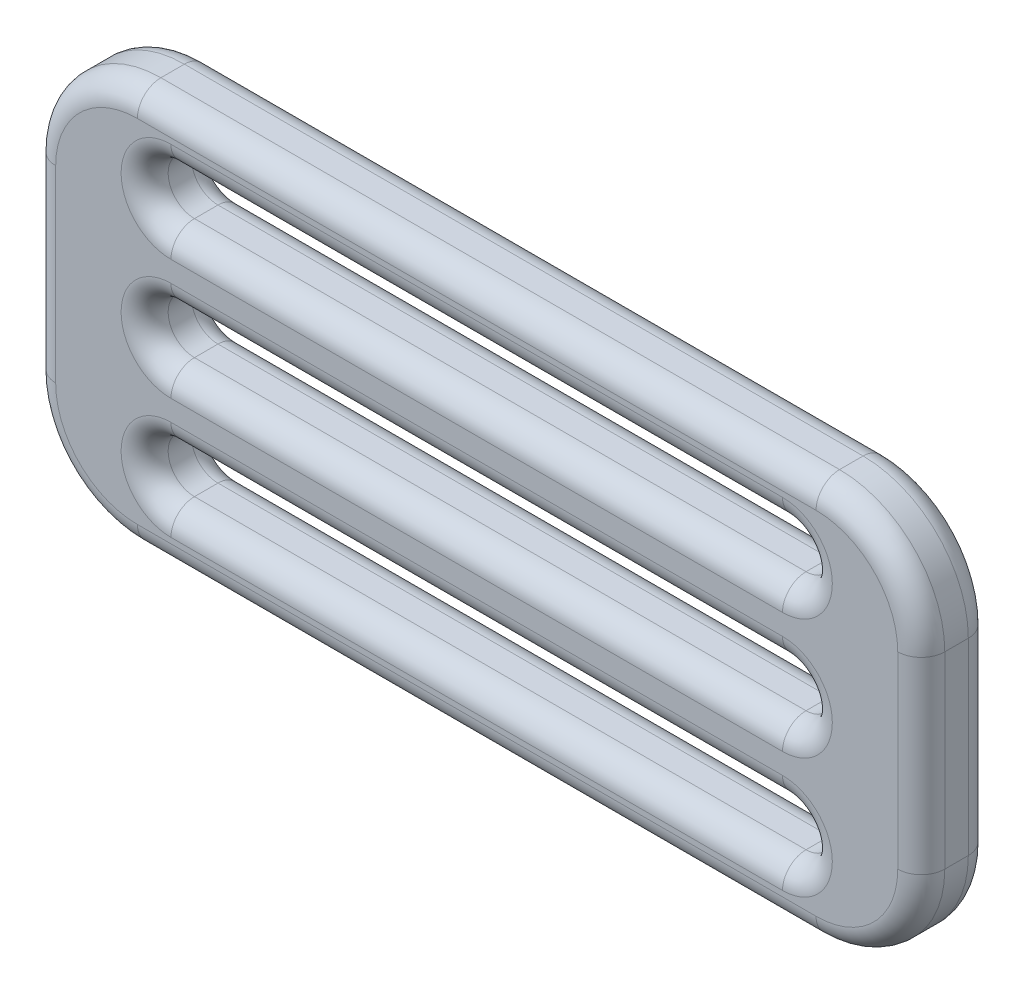
SolidWorks part; units mm, degrees
material "ABS"
ref_plane "Front Plane" through (0, 0, 0) normal (0, 0, 1) x (1, 0, 0)
ref_plane "Top Plane" through (0, 0, 0) normal (0, 1, 0) x (1, 0, 0)
ref_plane "Right Plane" through (0, 0, 0) normal (1, 0, 0) x (0, 0, -1)
ref_plane "Plane1" through (0, 0, 0.6) normal (0, 0, -1) x (-1, 0, 0)
sketch "Sketch1" plane through (0, 0, 0.6) normal (0, 0, -1) x (-1, 0, 0)
  line L0 (-4.4734, 35.787) -> (-33.3266, 35.787)
  line L1 (-37.8, 31.3136) -> (-37.8, 23.3136)
  line L2 (-33.3266, 18.8402) -> (-4.4734, 18.8402)
  line L3 (0, 23.3136) -> (0, 31.3136)
  line L4 (-5.9, 23.3136) -> (-31.9, 23.3136)
  line L5 (-18.9, 18.8402) -> (-18.9, 21.0769) construction
  line L6 (-18.9, 21.0769) -> (-18.9, 23.3136) construction
  line L7 (-18.9, 35.787) -> (-18.9, 28.2965) construction
  line L8 (-5.9, 32.4322) -> (-5.9, 22.1953) construction
  line L9 (-5.9, 26.1954) -> (-31.9, 26.1954)
  line L10 (-18.9, 26.1954) -> (-18.9, 28.4321) construction
  line L11 (-5.9, 28.4321) -> (-31.9, 28.4321)
  line L13 (-5.9, 21.0769) -> (-31.9, 21.0769)
  line L16 (-5.9, 31.3139) -> (-31.9, 31.3139)
  line L17 (-31.9, 33.5505) -> (-5.9, 33.5505)
  arc A0 (0, 31.3136) -> (-4.4734, 35.787) centre (-4.4734, 31.3136) ccw
  arc A1 (-33.3266, 35.787) -> (-37.8, 31.3136) centre (-33.3266, 31.3136) ccw
  arc A2 (-37.8, 23.3136) -> (-33.3266, 18.8402) centre (-33.3266, 23.3136) ccw
  arc A3 (-4.4734, 18.8402) -> (0, 23.3136) centre (-4.4734, 23.3136) ccw
  arc A4 (-5.9, 28.4321) -> (-5.9, 26.1954) centre (-5.9, 27.3137) cw
  arc A5 (-31.9, 26.1954) -> (-31.9, 28.4321) centre (-31.9, 27.3137) cw
  arc A21 (-5.9, 23.3136) -> (-5.9, 21.0769) centre (-5.9, 22.1953) cw
  arc A22 (-31.9, 21.0769) -> (-31.9, 23.3136) centre (-31.9, 22.1953) cw
  arc A24 (-5.9, 33.5505) -> (-5.9, 31.3139) centre (-5.9, 32.4322) cw
  arc A25 (-31.9, 31.3139) -> (-31.9, 33.5505) centre (-31.9, 32.4322) cw
  point P12 (-18.9, 33.5505)
  dimension "D1" = 37.8
  dimension "D2" = 2.2367
  dimension "D3" = 26
  dimension "D4" = 2.2367
  dimension "D5" = 26
  dimension "D6" = 2.2364
  dimension "D7" = 2.2367
  dimension "D8" = 1.1183
  dimension "D9" = 4.4734
  dimension "D10" = 4.4734
extrude "Boss-Extrude1" add sketch "Sketch1" against normal blind 3
fillet "Fillet1" radius 1 40 edges at (18.9, 35.787, 3.6) (36.4898, 34.4768, 3.6) (37.8, 27.3136, 3.6) (36.4898, 20.1505, 3.6) (18.9, 18.8402, 3.6) (1.3102, 20.1505, 3.6) (0, 27.3136, 3.6) (1.3102, 34.4768, 3.6) (33.0183, 22.1953, 3.6) (18.9, 23.3136, 3.6) (4.7817, 22.1953, 3.6) (18.9, 21.0769, 3.6) (33.0183, 32.4322, 3.6) (18.9, 33.5505, 3.6) (4.7817, 32.4322, 3.6) (18.9, 31.3139, 3.6) (0, 27.3136, 0.6) (1.3102, 20.1505, 0.6) (18.9, 18.8402, 0.6) (36.4898, 20.1505, 0.6) (37.8, 27.3136, 0.6) (36.4898, 34.4768, 0.6) (18.9, 35.787, 0.6) (1.3102, 34.4768, 0.6) (18.9, 23.3136, 0.6) (33.0183, 22.1953, 0.6) (18.9, 21.0769, 0.6) (4.7817, 22.1953, 0.6) (18.9, 33.5505, 0.6) (33.0183, 32.4322, 0.6) (18.9, 31.3139, 0.6) (4.7817, 32.4322, 0.6) (33.0183, 27.3137, 3.6) (18.9, 28.4321, 3.6) (4.7817, 27.3137, 3.6) (18.9, 26.1954, 3.6) (18.9, 28.4321, 0.6) (33.0183, 27.3137, 0.6) (18.9, 26.1954, 0.6) (4.7817, 27.3137, 0.6)
